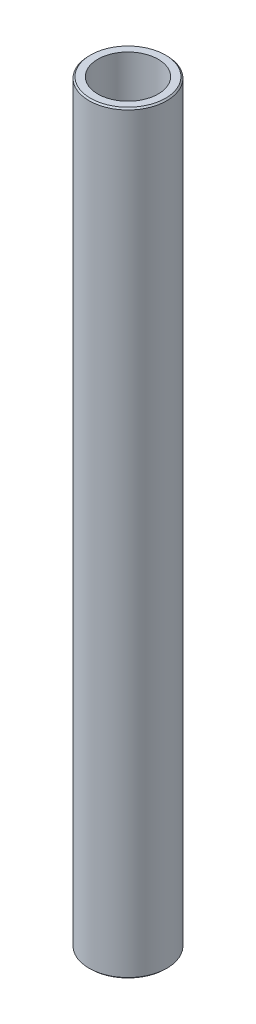
SolidWorks part; units mm, degrees
ref_plane "Front Plane" through (0, 0, 0) normal (0, 0, 1) x (1, 0, 0)
ref_plane "Top Plane" through (0, 0, 0) normal (0, 1, 0) x (1, 0, 0)
ref_plane "Right Plane" through (0, 0, 0) normal (1, 0, 0) x (0, 0, -1)
sketch "Sketch1" plane through (0, 0, 0) normal (0, 1, 0) x (1, 0, 0)
  circle A0 centre (0, 0) radius 20
  dimension "SHAFT_OD" = 40
extrude "Boss-Extrude1" add sketch "Sketch1" along normal blind 387.8648
sketch "Sketch2" plane through (0, 0, 0) normal (0, 1, 0) x (1, 0, 0)
  circle A0 centre (0, 0) radius 15.5213
  dimension "BORE_D" = 31.0427
extrude "Cut-Extrude1" cut sketch "Sketch2" along normal through all
chamfer "Chamfer1" distance 0.7397 angle 43.946 2 edges at (0, 387.8648, 20) (0, 0, 20) first distance on face at (0, 387.8648, 20) first distance on face at (0, 0, 15.5213)
